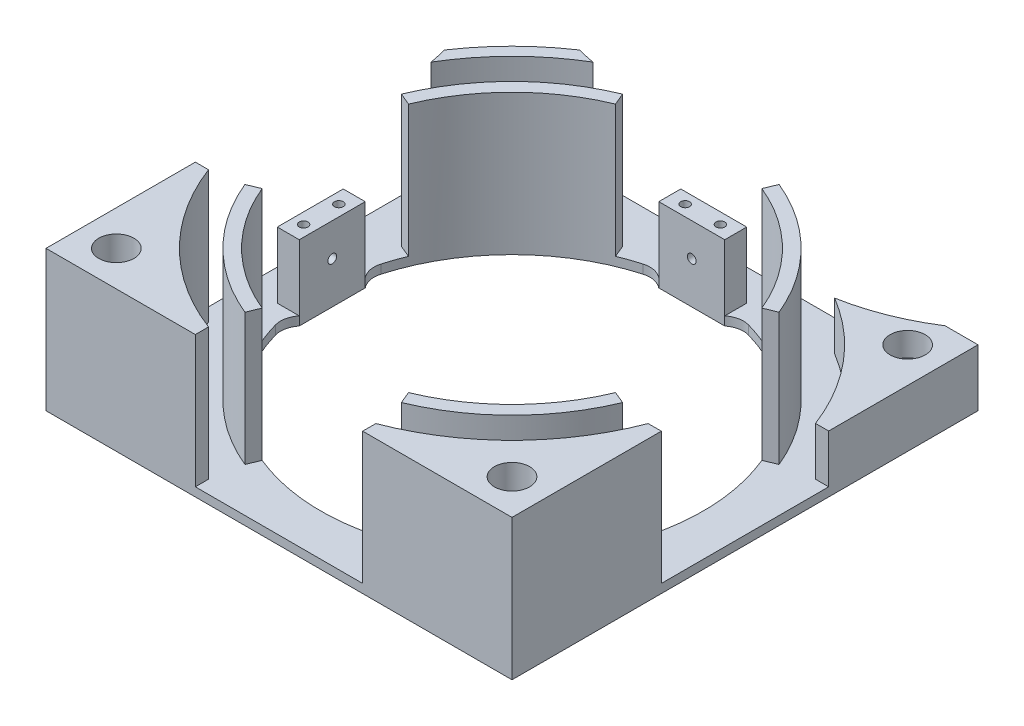
SolidWorks part; units mm, degrees
ref_plane "Front Plane" through (0, 0, 0) normal (0, 0, 1) x (1, 0, 0)
ref_plane "Top Plane" through (0, 0, 0) normal (0, 1, 0) x (1, 0, 0)
ref_plane "Right Plane" through (0, 0, 0) normal (1, 0, 0) x (0, 0, -1)
sketch "Sketch1" plane through (0, 0, 0) normal (0, 1, 0) x (1, 0, 0)
  line L1 (-53, -53) -> (53, -53)
  line L2 (-53, -53) -> (-53, 53)
  line L3 (-53, 53) -> (53, 53)
  line L4 (53, -53) -> (53, 53)
  line L5 (-53, -53) -> (53, 53) construction
  line L6 (-53, 53) -> (53, -53) construction
  point P0 (0, 0)
  dimension "D1" = 106
extrude "Boss-Extrude1" add sketch "Sketch1" along normal blind 2
sketch "Sketch2" plane through (0, 2, 0) normal (0, 1, 0) x (1, 0, 0)
  circle A0 centre (0, 0) radius 46.5
  circle A1 centre (0, 0) radius 43.5
  dimension "D2" = 93
  dimension "D1" = 3
extrude "Boss-Extrude2" add sketch "Sketch2" along normal blind 30
sketch "Sketch3" plane through (0, 2, 0) normal (0, 1, 0) x (1, 0, 0)
  circle A1 centre (0, 0) radius 43.5
  circle A2 centre (0, 0) radius 43.5
  dimension "D1" = 0
extrude "Cut-Extrude1" cut sketch "Sketch3" against normal up to next
sketch "Sketch4" plane through (0, 32, 0) normal (0, 1, 0) x (1, 0, 0)
  line L0 (-40.1888, 16.6467) -> (-42.9604, 17.7948)
  line L1 (-40.1888, -16.6467) -> (-42.9604, -17.7948)
  line L2 (-16.6467, -40.1888) -> (-17.7948, -42.9604)
  line L3 (16.6467, -40.1888) -> (17.7948, -42.9604)
  line L4 (40.1888, -16.6467) -> (42.9604, -17.7948)
  line L5 (40.1888, 16.6467) -> (42.9604, 17.7948)
  line L6 (16.6467, 40.1888) -> (17.7948, 42.9604)
  line L7 (-16.6467, 40.1888) -> (-17.7948, 42.9604)
  arc A0 (-40.1888, -16.6467) -> (-40.1888, 16.6467) centre (0, 0) cw
  circle A1 centre (0, 0) radius 43.5 construction
  arc A2 (-16.6467, 40.1888) -> (16.6467, 40.1888) centre (0, 0) cw
  arc A3 (40.1888, 16.6467) -> (40.1888, -16.6467) centre (0, 0) cw
  arc A4 (-16.6467, -40.1888) -> (16.6467, -40.1888) centre (0, 0) ccw
  circle A5 centre (0, 0) radius 46.5 construction
  circle A6 centre (0, 0) radius 46.5 construction
  arc A7 (-17.7948, 42.9604) -> (17.7948, 42.9604) centre (0, 0) cw
  arc A8 (42.9604, 17.7948) -> (42.9604, -17.7948) centre (0, 0) cw
  arc A9 (17.7948, -42.9604) -> (-17.7948, -42.9604) centre (0, 0) cw
  arc A10 (-42.9604, -17.7948) -> (-42.9604, 17.7948) centre (0, 0) cw
  point P12 (0, -43.5)
  point P13 (0, 43.5)
  point P14 (-43.5, 0)
  point P16 (43.5, 0)
  circle M11 centre (0, 0) radius 46.5
  circle M12 centre (0, 0) radius 43.5
  dimension "D1" = 45
extrude "Cut-Extrude2" cut sketch "Sketch4" against normal up to surface (30 mm away) contours L1 L0 M12 M11 | L7 L6 M12 M11 | L5 L4 M12 M11 | A4 L3 A9 L2 region at (-43.8685, 32, 0) region at (0, 32, -43.8685) region at (43.8685, 32, 0) up to face at (0, 2, -46.5)
sketch "Sketch5" plane through (0, 2, 0) normal (0, 1, 0) x (1, 0, 0)
  line L4 (-7.5, 40.8912) -> (-7.5, 45.8912)
  line L5 (7.5, 45.8912) -> (7.5, 40.8912)
  line L6 (-7.5, 45.8912) -> (7.5, 45.8912)
  line L7 (-7.5, 40.8912) -> (7.5, 40.8912)
  arc A2 (-7.5, 45.8912) -> (7.5, 45.8912) centre (0, 0) cw construction
  arc A4 (-17.7948, 42.9604) -> (-42.9604, 17.7948) centre (0, 0) ccw construction
  dimension "D1" = 15
  dimension "D2" = 5
extrude "Boss-Extrude3" add sketch "Sketch5" along normal blind 15 and the other way up to surface (2 mm away) other way up to face at (0, 0, -43.5)
fillet "Fillet1" radius 5 2 edges at (7.5, 1, -42.8486) (-7.5, 1, -42.8486)
pattern_circular "CirPattern1" count 2 every 90 about axis through (0, 32, 0) along (0, -1, 0) of "Boss-Extrude3", "Fillet1" reverse direction yes
sketch "Sketch6" plane through (0, 2, 0) normal (0, 1, 0) x (1, 0, 0)
  line L14 (53, -53) -> (53, 53) construction
  line L16 (50, -19.0329) -> (53, -19.0329)
  line L17 (53, -19.0329) -> (53, -53)
  line L18 (53, -53) -> (19.0329, -53)
  line L19 (-53, -53) -> (53, -53) construction
  line L20 (19.0329, -53) -> (19.0329, -50)
  line L21 (-19.0329, -50) -> (-19.0329, -53)
  line L22 (-19.0329, -53) -> (-53, -53)
  line L23 (-53, -53) -> (-53, -19.0329)
  line L24 (-53, 53) -> (-53, -53) construction
  line L25 (-53, -19.0329) -> (-50, -19.0329)
  arc A0 (50, -19.0329) -> (19.0329, -50) centre (0, 0) cw
  arc A1 (17.7948, -42.9604) -> (42.9604, -17.7948) centre (0, 0) ccw construction
  arc A2 (-50, -19.0329) -> (-19.0329, -50) centre (0, 0) ccw
  dimension "D1" = 7
  dimension "D2" = 3
extrude "Boss-Extrude4" add sketch "Sketch6" along normal up to surface (30 mm away) up to face at (30.6087, 32, 30.6087)
sketch "Sketch8" plane through (0, 2, 0) normal (0, 1, 0) x (1, 0, 0)
  line L0 (-53, 53) -> (-45.5, 53)
  line L1 (53, 53) -> (-53, 53) construction
  line L2 (-53, 53) -> (-53, 45.5)
  line L3 (-53, 53) -> (-53, -19.0329) construction
  line L4 (50, 19.0329) -> (53, 19.0329)
  line L5 (53, -19.0329) -> (53, 53) construction
  line L6 (53, 19.0329) -> (53, 53)
  line L7 (53, 53) -> (45.5, 53)
  line L8 (53, 53) -> (-53, 53) construction
  line L9 (53, -19.0329) -> (50, -19.0329) construction
  arc A0 (-45.8912, 27.5) -> (-27.5, 45.8912) centre (0, 0) cw
  arc A1 (-45.5, 53) -> (-27.5, 45.8912) centre (-18.4809, 95.071) ccw
  arc A2 (-53, 45.5) -> (-45.8912, 27.5) centre (-95.071, 18.4809) cw
  arc A4 (-50, -19.0329) -> (-19.0329, -50) centre (0, 0) ccw construction
  arc A5 (27.5, 45.8912) -> (50, 19.0329) centre (0, 0) cw
  arc A6 (45.5, 53) -> (27.5, 45.8912) centre (18.4809, 95.071) cw
  dimension "D1" = 50
  dimension "D2" = 7.5
extrude "Boss-Extrude5" add sketch "Sketch8" along normal up to surface (15 mm away) up to face at (-43.3912, 17, 0)
sketch "Sketch9" plane through (0, 17, 0) normal (0, 1, 0) x (1, 0, 0)
  line L0 (50, 19.0329) -> (53, 19.0329)
  arc A0 (-45.8912, 27.5) -> (-27.5, 45.8912) centre (0, 0) cw
  arc A1 (-45.5, 53) -> (-27.5, 45.8912) centre (-18.4809, 95.071) ccw construction
  arc A2 (-46.7627, 31.3768) -> (-31.3768, 46.7627) centre (0, 0) cw
  arc A3 (-45.8912, 27.5) -> (-53, 45.5) centre (-95.071, 18.4809) ccw construction
  arc A4 (-45.5, 53) -> (-27.5, 45.8912) centre (-18.4809, 95.071) ccw construction
  arc A5 (-31.3768, 46.7627) -> (-27.5, 45.8912) centre (-18.4809, 95.071) ccw
  arc A6 (-46.7627, 31.3768) -> (-45.8912, 27.5) centre (-95.071, 18.4809) cw
  arc A7 (-45.8912, 27.5) -> (-53, 45.5) centre (-95.071, 18.4809) ccw construction
  arc A8 (27.5, 45.8912) -> (50, 19.0329) centre (0, 0) cw
  arc A9 (50, 19.0329) -> (27.5, 45.8912) centre (0, 0) ccw construction
  arc A10 (31.3768, 46.7627) -> (53, 19.0329) centre (0, 0) cw
  arc A11 (27.5, 45.8912) -> (45.5, 53) centre (18.4809, 95.071) ccw construction
  arc A12 (27.5, 45.8912) -> (31.3768, 46.7627) centre (18.4809, 95.071) ccw
extrude "Boss-Extrude6" add sketch "Sketch9" along normal up to surface (15 mm away) up to face at (-30.6087, 32, -30.6087)
hole_wizard "CBORE for M4 Hex Socket Head Cap Screw1" positions "Sketch13" profile "Sketch11" counterbore size "M4" standard "DIN" end condition up to next
sketch "Sketch13" plane through (0, 32, 0) normal (0, 1, 0) x (1, 0, 0)
  line L2 (-53, 45.5) -> (-53, 53) construction
  line L3 (-53, 53) -> (-45.5, 53) construction
  line L4 (19.0329, -53) -> (53, -53) construction
  line L6 (53, -53) -> (53, -19.0329) construction
  point P0 (-45, -45)
  point P2 (45, -45)
  point P4 (45, 45)
  point P6 (-45, 45)
  dimension "D1" = 8
  dimension "D2" = 8
  dimension "D3" = 8
  dimension "D4" = 8
sketch "Sketch11" plane through (-45, 32, 45) normal (1, 0, 0) x (0, 0, 1)
  line L0 (0, 0) -> (0, 32)
  line L1 (0, 32) -> (2.25, 32)
  line L3 (2.25, 32) -> (2.25, 24.4)
  line L4 (2.25, 24.4) -> (4, 24.4)
  line L5 (4, 24.4) -> (4, 0)
  line L7 (4, 0) -> (0, 0)
  line L11 (0, -6.35) -> (0, 107.95) construction
  dimension "Thru Hole Dia." = 4.5
  dimension "Thru Hole Depth" = 32
  dimension "C'Bore Dia." = 8
  dimension "C'Bore Depth" = 24.4
sketch "Sketch14" plane through (0, 32, 0) normal (0, 1, 0) x (1, 0, 0)
  line L0 (50, 19.0329) -> (53, 19.0329)
  line L1 (53, 19.0329) -> (53, 53)
  line L2 (53, 53) -> (45.5, 53)
  line L3 (45.5, 53) -> (27.5, 45.8912)
  line L4 (50, 19.0329) -> (27.5, 45.8912)
extrude "Cut-Extrude4" cut sketch "Sketch14" against normal offset from surface (19 mm away) 13 up to face at (-45, 0, 42.75)
sketch "Sketch15" plane through (0, 0, -45.8912) normal (0, 0, -1) x (-1, 0, 0)
  line L0 (-45.5, 2) -> (45.5, 2) construction
  circle A0 centre (0, 9.5) radius 1
  dimension "D1" = 2
  dimension "D2" = 7.5
extrude "Cut-Extrude5" cut sketch "Sketch15" against normal up to next
sketch "Sketch16" plane through (-45.8912, 0, 0) normal (-1, 0, 0) x (0, 0, 1)
  line L1 (7.5, 2) -> (-7.5, 2) construction
  circle A0 centre (0, 9.5) radius 1
  dimension "D1" = 2
  dimension "D2" = 7.5
extrude "Cut-Extrude6" cut sketch "Sketch16" against normal up to next
sketch "Sketch17" plane through (0, 17, 0) normal (0, 1, 0) x (1, 0, 0)
  line L0 (-40.8912, 7.5) -> (-45.8912, 7.5) construction
  line L1 (-7.5, 45.8912) -> (-7.5, 40.8912) construction
  circle A0 centre (4, 43.3912) radius 1
  circle A1 centre (-4, 43.3912) radius 1
  circle A2 centre (-43.3912, 4) radius 1
  circle A3 centre (-43.3912, -4) radius 1
  point P14 (-43.3912, 7.5)
  point P18 (-7.5, 43.3912)
  dimension "D1" = 2
  dimension "D2" = 8
  dimension "D3" = 4
  dimension "D4" = 8
  dimension "D5" = 4
extrude "Cut-Extrude7" cut sketch "Sketch17" against normal blind 10
